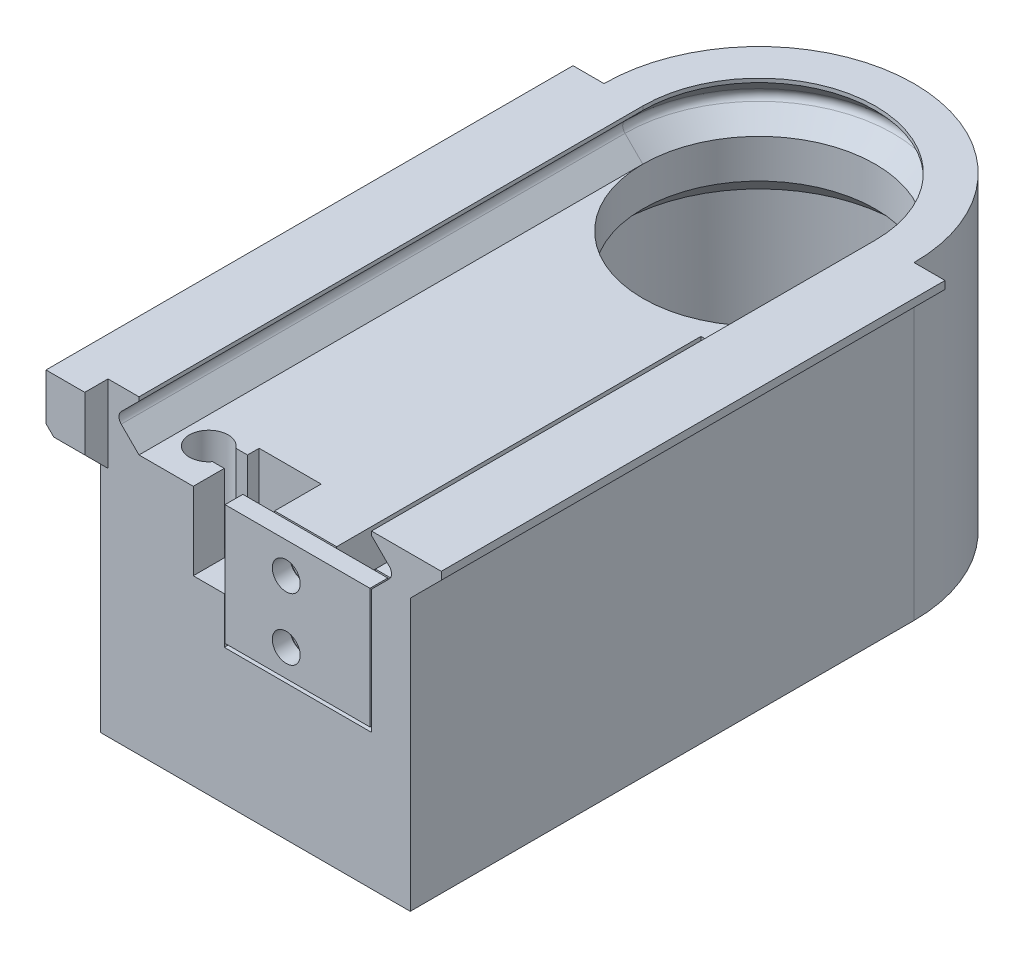
SolidWorks part; units mm, degrees
ref_plane "Płaszczyzna przednia" through (0, 0, 0) normal (0, 0, 1) x (1, 0, 0)
ref_plane "Płaszczyzna górna" through (0, 0, 0) normal (0, 1, 0) x (1, 0, 0)
ref_plane "Płaszczyzna prawa" through (0, 0, 0) normal (1, 0, 0) x (0, 0, -1)
sketch "Szkic1" plane through (0, 0, 0) normal (0, 1, 0) x (1, 0, 0)
  line L0 (0, -32.5) -> (0, 52.5) construction
  line L1 (-20, 32.5) -> (20, 32.5)
  line L2 (-20, 32.5) -> (-20, -32.5)
  line L3 (-20, -32.5) -> (20, -32.5)
  line L4 (20, 32.5) -> (20, -32.5)
  line L5 (-20, 32.5) -> (20, -32.5) construction
  line L6 (-20, -32.5) -> (20, 32.5) construction
  circle A0 centre (0, 32.5) radius 20
  point P0 (0, 0)
  dimension "D1" = 40
  dimension "D2" = 85
extrude "Dodanie-wyciągnięcie1" add sketch "Szkic1" along normal blind 40 contours A0 L2 L3 L4 | L1 A0 | A0 region at (0, 0, -40.9883) region at (0, 0, 7.6519)
sketch "Szkic2" plane through (0, 40, 0) normal (0, 1, 0) x (1, 0, 0)
  line L3 (-15, -32.5) -> (15, -32.5)
  line L5 (15, -32.5) -> (15, 32.5)
  line L6 (-15, 32.5) -> (-15, -32.5)
  line L7 (15, -32.5) -> (15, 32.5)
  line L8 (-15, 32.5) -> (-15, -32.5)
  arc A5 (15, 32.5) -> (-15, 32.5) centre (0, 32.5) ccw
  arc A6 (15, 32.5) -> (-15, 32.5) centre (0, 32.5) ccw
  dimension "D1" = 5
extrude "Wytnij-wyciągnięcie1" cut sketch "Szkic2" against normal blind 6.5
sketch "Szkic4" plane through (0, 0, 32.5) normal (0, 0, 1) x (1, 0, 0)
  line L0 (15, 33.5) -> (18, 36.5)
  line L1 (18, 36.5) -> (15, 39.5)
  line L2 (15, 33.5) -> (15, 40) construction
  line L3 (15, 39.5) -> (15, 33.5)
  dimension "D1" = 6
  dimension "D2" = 45
sketch "Szkic5" plane through (0, 40, 0) normal (0, 1, 0) x (1, 0, 0)
  line L0 (15, -32.5) -> (15, 32.5) construction
  line L1 (-15, 32.5) -> (-15, -32.5) construction
  line L2 (15, -32.5) -> (15, 32.5)
  line L3 (-15, 32.5) -> (-15, -32.5)
  arc A0 (15, 32.5) -> (-15, 32.5) centre (0, 32.5) ccw construction
  arc A1 (15, 32.5) -> (-15, 32.5) centre (0, 32.5) ccw
sweep "Wycięcie-wyciągnięcie po ścieżce1" cut profiles "Szkic4" path "Szkic5"
sketch "Szkic6" plane through (0, 33.5, 0) normal (0, 1, 0) x (1, 0, 0)
  circle A0 centre (0, 32.5) radius 15
extrude "Wytnij-wyciągnięcie2" cut sketch "Szkic6" against normal blind 30
sketch "Szkic7" plane through (0, 3.5, 0) normal (0, 1, 0) x (1, 0, 0)
  circle A0 centre (0, 32.5) radius 18
  arc A5 (20, 32.5) -> (-20, 32.5) centre (0, 32.5) ccw construction
  dimension "D1" = 2
extrude "Wytnij-wyciągnięcie4" cut sketch "Szkic7" along normal blind 20
chamfer "Sfazowanie1" distance 5 angle 45 1 edges at (0, 23.5, -17.5)
sketch "Szkic8" plane through (0, 33.5, 0) normal (0, 1, 0) x (1, 0, 0)
  line L0 (-15, -32.5) -> (15, -32.5) construction
  line L1 (13, 17) -> (8, 17)
  line L2 (13, 17) -> (13, -30)
  line L3 (13, -30) -> (8, -30)
  line L4 (8, 17) -> (8, -30)
  line L5 (13, 17) -> (8, -30) construction
  line L6 (13, -30) -> (8, 17) construction
  line L7 (15, -32.5) -> (15, 32.5) construction
  point P0 (10.5, -6.5)
  dimension "D1" = 5
  dimension "D2" = 2.5
  dimension "D3" = 47
  dimension "D4" = 2
extrude "Wytnij-wyciągnięcie5" cut sketch "Szkic8" against normal blind 5
fillet "Zaokrąglenie2" radius 1 3 edges at (-18, 36.5, 0) (0, 36.5, -50.5) (18, 36.5, 0)
ref_plane "Płaszczyzna1" through (15, 40, 32.5) normal (0, 0, -1) x (-1, 0, 0)
sketch "Szkic10" plane through (0, 33.5, 0) normal (0, 1, 0) x (1, 0, 0)
  line L0 (-4, -27) -> (-11.5, -27) construction
  line L1 (0, -30) -> (-8, -30)
  line L2 (0, -30) -> (0, -24)
  line L3 (0, -24) -> (-8, -24)
  line L4 (-8, -30) -> (-8, -24)
  line L5 (0, -30) -> (-8, -24) construction
  line L6 (0, -24) -> (-8, -30) construction
  line L7 (8, -30) -> (13, -30) construction
  line L8 (-9.5, -25.5) -> (-8, -25.5)
  line L9 (-9.5, -25.5) -> (-9.5, -28.5)
  line L10 (-9.5, -28.5) -> (-8, -28.5)
  line L11 (-8, -25.5) -> (-8, -28.5)
  line L12 (-9.5, -25.5) -> (-8, -28.5) construction
  line L13 (-9.5, -28.5) -> (-8, -25.5) construction
  line L14 (0, 0) -> (0, -32.5) construction
  line L15 (32.875, -32.5) -> (-2.875, -32.5) construction
  circle A0 centre (-11.5, -27) radius 2.5
  point P0 (-4, -27)
  point P8 (-8.75, -27)
  dimension "D3" = 5
  dimension "D1" = 8
  dimension "D2" = 6
  dimension "D4" = 1.5
  dimension "D5" = 3
extrude "Wytnij-wyciągnięcie6" cut sketch "Szkic10" against normal blind 10 contours L9 A0 | L4 L1 L2 L3 | A0 L10 L4 L8 | L9 A0 region at (-4, 33.5, 27) region at (-8.5889, 33.5, 27) region at (-11.6209, 33.5, 27) region at (-9.2982, 33.5, 27)
sketch "Szkic11" plane through (0, 23.5, 0) normal (0, 1, 0) x (1, 0, 0)
  circle A0 centre (-11.5, -27) radius 2.5
extrude "Wytnij-wyciągnięcie7" cut sketch "Szkic11" against normal blind 21
sketch "Szkic12" plane through (0, 33.5, 0) normal (0, 1, 0) x (1, 0, 0)
  line L0 (-15, -32.5) -> (15, -32.5) construction
  line L1 (-8, -30) -> (-4, -30)
  line L2 (-8, -30) -> (-8, -32.5)
  line L3 (-8, -32.5) -> (-4, -32.5)
  line L4 (-4, -30) -> (-4, -32.5)
  dimension "D1" = 4
extrude "Wytnij-wyciągnięcie8" cut sketch "Szkic12" against normal up to surface (10 mm away) up to face at (-6.3125, 23.5, 27)
sketch "Szkic13" plane through (0, 0, 32.5) normal (0, 0, 1) x (1, 0, 0)
  line L0 (-20, 40) -> (-24, 40)
  line L1 (-20, 40) -> (-20, 0) construction
  line L2 (-24, 40) -> (-24, 39)
  line L3 (-24, 39) -> (-20, 35)
  line L4 (-20, 35) -> (-20, 40)
  line L5 (0, 0) -> (0, 45.7075) construction
  line L6 (-20, 0) -> (20, 0) construction
  line L7 (20, 35) -> (20, 40)
  line L8 (24, 39) -> (20, 35)
  line L9 (24, 40) -> (24, 39)
  line L10 (20, 40) -> (24, 40)
  dimension "D1" = 4
  dimension "D2" = 1
  dimension "D3" = 45
extrude "Dodanie-wyciągnięcie2" add sketch "Szkic13" against normal up to vertex (65 mm away) up to point (-20, 40, -32.5)
sketch "Szkic16" plane through (0, 0, 32.5) normal (0, 0, 1) x (1, 0, 0)
  line L0 (-24, 40) -> (-24, 39) construction
  line L1 (-24, 40) -> (-19, 40)
  line L2 (-24, 40) -> (-24, 30)
  line L3 (-24, 30) -> (-19, 30)
  line L4 (-19, 40) -> (-19, 30)
  dimension "D1" = 5
  dimension "D2" = 10
extrude "Dodanie-wyciągnięcie3" add sketch "Szkic16" along normal blind 3
chamfer "Sfazowanie4" distance 4 angle 45 1 edges at (-24, 30, 34)
chamfer "Sfazowanie5" distance 3 angle 45 1 edges at (-19.5, 30, 35.5)
sketch "Szkic17" plane through (0, 33.5, 0) normal (0, 1, 0) x (1, 0, 0)
  line L0 (15, -32.5) -> (15, 32.5) construction
  line L1 (-4, -32.5) -> (15, -32.5)
  line L2 (-4, -32.5) -> (-4, -30)
  line L3 (-4, -30) -> (15, -30)
  line L4 (15, -32.5) -> (15, -30)
  line L5 (8, -30) -> (13, -30) construction
extrude "Wytnij-wyciągnięcie9" cut sketch "Szkic17" against normal blind 16
sketch "Szkic18" plane through (0, 0, 30) normal (0, 0, 1) x (1, 0, 0)
  line L3 (8, 33.5) -> (0, 33.5) construction
  line L4 (15, 17.5) -> (-4, 17.5) construction
  line L6 (4, 29.5) -> (4, 33.5) construction
  line L7 (4, 29.5) -> (4, 21.5) construction
  line L8 (4, 21.5) -> (4, 17.5) construction
  circle A0 centre (4, 29.5) radius 2
  circle A1 centre (4, 21.5) radius 2
  point P6 (4, 29.5)
  point P8 (4, 21.5)
  dimension "D1" = 4
  dimension "D2" = 8
sketch "Szkic22" plane through (0, 0, 30) normal (0, 0, 1) x (1, 0, 0)
  point P0 (4, 29.5)
  point P3 (4, 21.5)
hole_wizard "Otwory ustalające Ø4.0mm5" positions "Szkic22" profile "Szkic21" hole size "Ø4.0" standard "DIN"
sketch "Szkic21" plane through (4, 29.5, 30) normal (1, 0, 0) x (0, -1, 0)
  line L0 (0, 0) -> (0, 16.2017)
  line L1 (0, 16.2017) -> (2, 15)
  line L2 (2, 15) -> (2, 0)
  line L5 (2, 0) -> (0, 0)
  line L10 (0, 16.2017) -> (-2, 15) construction
  line L11 (0, -6.35) -> (0, 107.95) construction
  dimension "Średnica otworu" = 4
  dimension "Głębokość otworu" = 15
  dimension "Kąt wiertła" = 118
sketch "Szkic23" plane through (0, 33.5, 0) normal (0, 1, 0) x (1, 0, 0)
  line L1 (-3.9, -30.2) -> (14.8, -30.2)
  line L2 (-3.9, -30.2) -> (-3.9, -32.5)
  line L3 (-3.9, -32.5) -> (14.8, -32.5)
  line L4 (-4, -30) -> (-4, -32.5)
  line L5 (-4, -32.5) -> (15, -32.5)
  line L6 (15, -32.5) -> (15, -30)
  line L7 (15, -30) -> (-4, -30)
  line L8 (-4, -30) -> (-4, -32.5) construction
  line L9 (-4, -32.5) -> (15, -32.5) construction
  line L10 (15, -32.5) -> (15, -30) construction
  line L11 (15, -30) -> (-4, -30) construction
  line L12 (14.8, -30.2) -> (14.8, -32.5)
  dimension "D2" = 0.2
  dimension "D3" = 0.2
  dimension "D4" = 0.2
  dimension "D1" = 0
extrude "Dodanie-wyciągnięcie4" add sketch "Szkic23" against normal blind 15.5 separate body
sketch "Szkic24" plane through (0, 0, 32.5) normal (0, 0, 1) x (1, 0, 0)
  circle A0 centre (4, 21.5) radius 2 construction
  circle A1 centre (4, 29.5) radius 2 construction
  circle A2 centre (4, 21.5) radius 2
  circle A3 centre (4, 29.5) radius 2
  point P0 (4, 21.5)
  point P2 (4, 29.5)
hole_wizard "Otwory ustalające Ø4.0mm6" positions "Szkic24" profile "Szkic25" hole size "Ø4.0" standard "DIN"
sketch "Szkic25" plane through (4, 21.5, 32.5) normal (1, 0, 0) x (0, -1, 0)
  line L0 (0, 0) -> (0, 16.0815)
  line L1 (0, 16.0815) -> (1.8, 15)
  line L2 (1.8, 15) -> (1.8, 0)
  line L5 (1.8, 0) -> (0, 0)
  line L10 (0, 16.0815) -> (-1.8, 15) construction
  line L11 (0, -6.35) -> (0, 107.95) construction
  dimension "Średnica otworu" = 3.6
  dimension "Głębokość otworu" = 15
  dimension "Kąt wiertła" = 118
